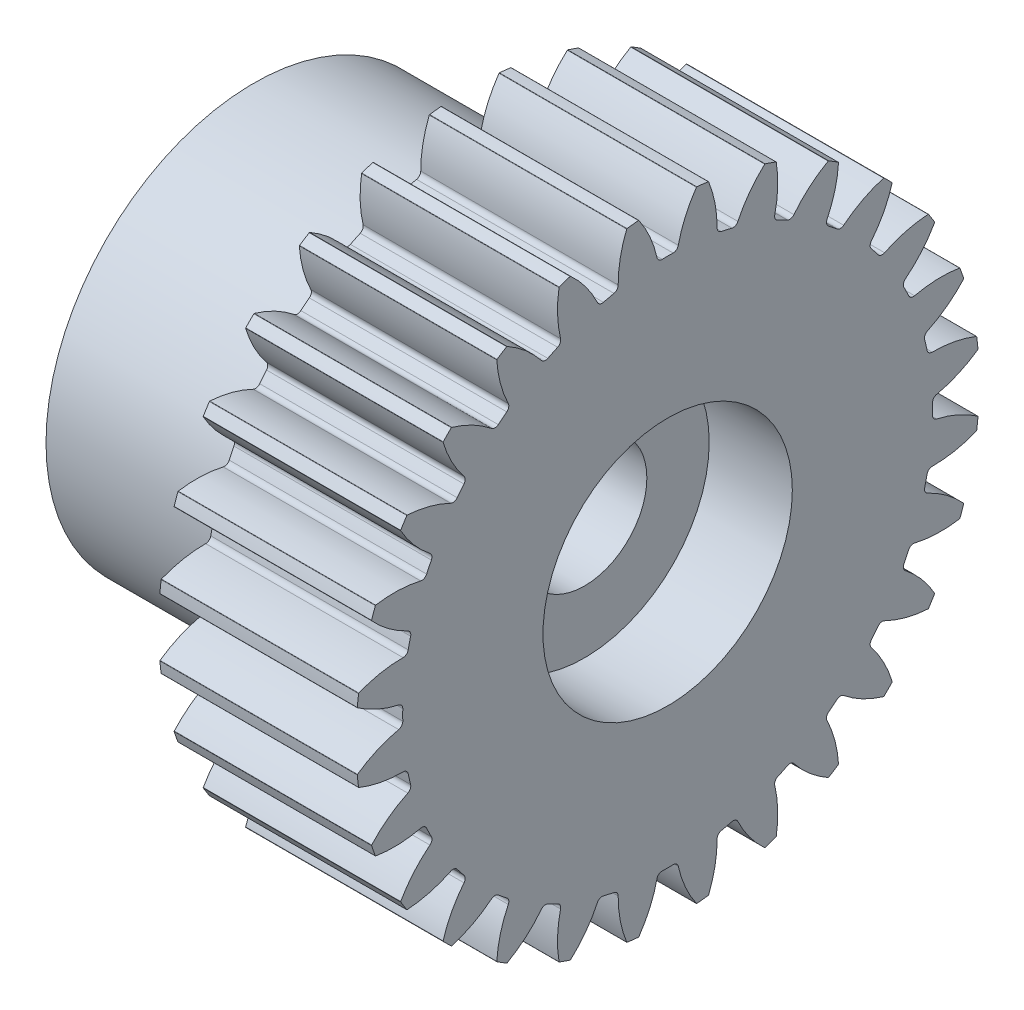
SolidWorks part; units mm, degrees
ref_plane "Plane1" through (0, 0, 0) normal (0, 0, 1) x (1, 0, 0)
ref_plane "Plane2" through (0, 0, 0) normal (0, 1, 0) x (1, 0, 0)
ref_plane "Plane3" through (0, 0, 0) normal (1, 0, 0) x (0, 0, -1)
other "Configuration Table"
sketch "HoldingSke" plane through (0, 0, 0) normal (0, 1, 0) x (1, 0, 0)
  line L0 (0, 0) -> (1.7659, -0.9389)
  line L1 (-15, 0) -> (100, 0) construction
  line L2 (0, 0) -> (-2.1039, 2.3779)
  line L3 (0, 0) -> (-11.863, 4.5341)
  line L4 (0, 0) -> (7.6251, 4.0544)
  line L5 (0, 0) -> (-46.8476, -17.4728)
  line L6 (0, 0) -> (-4.1448, -2.7965)
  line L7 (-2.1039, 2.3779) -> (8.6586, 51.2059)
  line L8 (-76.2, 54.61) -> (-75.9, 54.61)
  line L9 (-71.009, 38.7566) -> (-53.1078, 45.2721)
  line L10 (-76.2, 71.12) -> (104.1128, 71.12)
  line L11 (0, 0) -> (-5, 0)
  line L12 (-76.2, 101.6) -> (-76.181, 101.6)
  line L13 (24.9733, 27.94) -> (52.9518, 28.4284)
  line L14 (24.9733, 27.94) -> (24.9743, 27.94)
  line L15 (24.9733, 27.94) -> (100.4006, 29.5858)
  line L16 (-63.627, -0.5) -> (-12.827, -0.5)
  circle A0 centre (0, 0) radius 1.5
  circle A1 centre (0, 0) radius 6.374
  circle A2 centre (0, 0) radius 37.5
  circle A3 centre (0, 0) radius 1.5
  dimension "Num_teeth" = 28
  dimension "Pitch_radius" = 180.3128
  dimension "Width" = 5
  dimension "Thickness" = 5
sketch "BasProSke" plane through (0, 0, 0) normal (0, 1, 0) x (1, 0, 0)
  line L0 (-10, 0) -> (60, 0) construction
  line L1 (0, 0) -> (0, 7.5)
  line L2 (0, 0) -> (5, 0)
  line L3 (5, 0) -> (5, 7.5)
  line L4 (5, 7.5) -> (0, 7.5)
  dimension "Thickness" = 5
  dimension "Diameter" = 15
revolve "Base-Revolve" add sketch "BasProSke" angle 360 about L0
sketch "TooCutSke" plane through (0, 0, 0) normal (1, 0, 0) x (0, 0, -1)
  line L1 (0, 0) -> (0, 107) construction
  line L2 (0, 0) -> (-0.4257, 6.987) construction
  line L3 (0, 0) -> (-1.5654, 13.8936) construction
  line L4 (-0.4257, 6.987) -> (-0.7827, 6.9468) construction
  arc A0 (0.2356, 6.3696) -> (-0.2356, 6.3696) centre (0, 0) ccw
  arc A1 (0.7134, 7.4915) -> (-0.7134, 7.4915) centre (0, 0) ccw
  circle A2 centre (0, 0) radius 7 construction
  circle A3 centre (0, 0) radius 6.5778 construction
  arc A4 (-0.2356, 6.3696) -> (-0.7134, 7.4915) centre (-2.9887, 5.8597) ccw
  arc A5 (0.7134, 7.4915) -> (0.2356, 6.3696) centre (2.9887, 5.8597) ccw
extrude "ToothCut" cut sketch "TooCutSke" along normal through all
fillet "Breaks" radius 0.01 2 edges at (2.5, 7.4676, -0.6965) (2.5, 7.4676, 0.6965) tangent propagation no
fillet "RootFillets" radius 0.126 2 edges at (2.5, 6.3696, -0.2356) (2.5, 6.3696, 0.2356)
pattern_circular "TeethCuts" count 28 every 12.857 about axis through (-10, 0, 0) along (1, 0, 0) of "ToothCut", "RootFillets", "Breaks"
sketch "HubNeaOneSke" plane through (0, 0, 0) normal (-1, 0, 0) x (0, 0, 1)
  circle A0 centre (0, 0) radius 6.374
  dimension "Diameter" = 12.748
extrude "HubNearOne" add sketch "HubNeaOneSke" along normal blind 5.2067
sketch "HubNeaBotSke" plane through (0, 0, 0) normal (-1, 0, 0) x (0, 0, 1)
  circle A0 centre (0, 0) radius 6.374
  dimension "Diameter" = 12.748
extrude "HubNearBoth" [suppressed] add sketch "HubNeaBotSke" along normal blind 22.5
ref_plane "FarPln" through (5, 0, 0) normal (1, 0, 0) x (0, 0, -1)
sketch "HubFarSke" plane through (5, 0, 0) normal (1, 0, 0) x (0, 0, -1)
  circle A0 centre (0, 0) radius 6.374
  dimension "Diameter" = 12.748
extrude "HubFar" [suppressed] add sketch "HubFarSke" along normal blind 22.5
sketch "BorSke" plane through (0, 0, 0) normal (1, 0, 0) x (0, 0, -1)
  circle A0 centre (0, 0) radius 1.5
  dimension "Diameter" = 3
extrude "Bore" cut sketch "BorSke" along normal mid plane 100.0001
sketch "KeySke" plane through (0, 0, 0) normal (1, 0, 0) x (0, 0, -1)
  line L0 (-0.4, 0) -> (-0.4, 1.8)
  line L1 (-0.4, 1.8) -> (0.4, 1.8)
  line L2 (0.4, 1.8) -> (0.4, 0)
  line L3 (0, 0) -> (0, 34) construction
  line L4 (-0.4, 0) -> (0.4, 0)
  dimension "Width" = 0.8
extrude "Keyway" [suppressed] cut sketch "KeySke" along normal mid plane 100.0001
pattern_circular "Keyway2" [suppressed] count 2 every 90 about axis through (-10, 0, 0) along (1, 0, 0)
sketch "Sketch1" plane through (-5.2067, 0, 0) normal (-1, 0, 0) x (0, 0, 1)
  circle A0 centre (0, 0) radius 6.374
  circle A1 centre (0, 0) radius 5
  dimension "D1" = 10
extrude "Cut-Extrude1" cut sketch "Sketch1" along direction (-1, 0, 0) on the side against the normal up to surface (5.2067 mm away) up to face at (0, 3.6989, -5.8867)
sketch "Sketch2" plane through (5, 0, 0) normal (1, 0, 0) x (0, 0, -1)
  circle A0 centre (0, 0) radius 3
  dimension "D1" = 6
extrude "Cut-Extrude2" cut sketch "Sketch2" against normal blind 2.25
sketch "Sketch5" plane through (-5.2067, 0, 0) normal (-1, 0, 0) x (0, 0, 1)
  line L0 (0, 0) -> (0, 4) construction
  line L1 (0, 0) -> (0.5013, 3.9685) construction
  line L2 (0, 0) -> (0.9812, 3.8778) construction
  line L3 (0, 4.3946) -> (0.4598, 3.6401)
  line L4 (0.4598, 3.6401) -> (1.072, 4.2773)
  line L5 (0, 4.3946) -> (1.072, 4.2773)
  line L6 (1.072, 4.2773) -> (1.3297, 3.4321)
  line L7 (1.3297, 3.4321) -> (2.0811, 3.8971)
  line L8 (2.0811, 3.8971) -> (2.1206, 3.0144)
  line L9 (2.1206, 3.0144) -> (2.964, 3.2779)
  line L10 (2.964, 3.2779) -> (2.7827, 2.4131)
  line L11 (2.7827, 2.4131) -> (3.6651, 2.4585)
  line L12 (3.6651, 2.4585) -> (3.2745, 1.666)
  line L13 (3.2745, 1.666) -> (4.1405, 1.4906)
  line L14 (4.1405, 1.4906) -> (3.565, 0.8201)
  line L15 (3.565, 0.8201) -> (4.3602, 0.4349)
  line L16 (4.3602, 0.4349) -> (3.636, -0.0715)
  line L17 (3.636, -0.0715) -> (4.3104, -0.6424)
  line L18 (4.3104, -0.6424) -> (3.4831, -0.9527)
  line L19 (3.4831, -0.9527) -> (3.9943, -1.6734)
  line L20 (3.9943, -1.6734) -> (3.1158, -1.7682)
  line L21 (3.1158, -1.7682) -> (3.4318, -2.5934)
  line L22 (3.4318, -2.5934) -> (2.5573, -2.4668)
  line L23 (2.5573, -2.4668) -> (2.6581, -3.3446)
  line L24 (2.6581, -3.3446) -> (1.8426, -3.0045)
  line L25 (1.8426, -3.0045) -> (1.7219, -3.8798)
  line L26 (1.7219, -3.8798) -> (1.0166, -3.3475)
  line L27 (1.0166, -3.3475) -> (0.682, -4.1653)
  line L28 (0.682, -4.1653) -> (0.1313, -3.4744)
  line L29 (0.1313, -3.4744) -> (-0.3962, -4.1833)
  line L30 (-0.3962, -4.1833) -> (-0.7578, -3.3771)
  line L31 (-0.7578, -3.3771) -> (-1.445, -3.9326)
  line L32 (-1.445, -3.9326) -> (-1.5948, -3.0618)
  line L33 (-1.5948, -3.0618) -> (-2.3985, -3.4289)
  line L34 (-2.3985, -3.4289) -> (-2.327, -2.5482)
  line L35 (-2.327, -2.5482) -> (-3.1968, -2.7039)
  line L36 (-3.1968, -2.7039) -> (-2.9086, -1.8687)
  line L37 (-2.9086, -1.8687) -> (-3.7897, -1.8032)
  line L38 (-3.7897, -1.8032) -> (-3.3028, -1.0659)
  line L39 (-3.3028, -1.0659) -> (-4.14, -0.7833)
  line L40 (-4.14, -0.7833) -> (-3.485, -0.1903)
  line L41 (-3.485, -0.1903) -> (-4.2257, 0.2916)
  line L42 (-4.2257, 0.2916) -> (-3.4438, 0.7032)
  line L43 (-3.4438, 0.7032) -> (-4.0413, 1.3541)
  line L44 (-4.0413, 1.3541) -> (-3.1816, 1.5583)
  line L45 (-3.1816, 1.5583) -> (-3.5985, 2.3374)
  line L46 (-3.5985, 2.3374) -> (-2.715, 2.3214)
  line L47 (-2.715, 2.3214) -> (-2.9251, 3.1796)
  line L48 (-2.9251, 3.1796) -> (-2.0734, 2.9444)
  line L49 (-2.0734, 2.9444) -> (-2.0633, 3.8279)
  line L50 (-2.0633, 3.8279) -> (-1.2969, 3.3883)
  line L51 (-1.2969, 3.3883) -> (-1.0675, 4.2416)
  line L52 (-1.0675, 4.2416) -> (-0.4344, 3.6251)
  line L53 (-0.4344, 3.6251) -> (0, 4.3946)
  line L54 (0.0718, 0.0932) -> (0.4598, 3.6401) construction
  arc A0 (-2.837, 2.8198) -> (-3.2506, 2.3311) centre (0, 0) ccw
  arc A1 (5.1949, 5.4025) -> (4.2351, 4.8995) centre (5.9901, 2.7178) ccw construction
  arc A2 (5.1949, 5.4025) -> (4.2351, 4.8995) centre (5.9901, 2.7178) ccw
  arc A3 (-3.44, 2.0412) -> (-3.737, 1.4264) centre (0, 0) ccw
  arc A4 (-3.8367, 1.1312) -> (-3.9777, 0.4222) centre (0, 0) ccw
  arc A5 (-3.9974, 0.1431) -> (-3.9526, -0.6137) centre (0, 0) ccw
  arc A6 (-3.9059, -0.8623) -> (-3.6619, -1.6096) centre (0, 0) ccw
  arc A7 (-3.5619, -1.8201) -> (-3.1252, -2.4966) centre (0, 0) ccw
  arc A8 (-2.9824, -2.6656) -> (-2.3811, -3.2141) centre (0, 0) ccw
  arc A9 (-2.2022, -3.3392) -> (-1.4824, -3.7152) centre (0, 0) ccw
  arc A10 (-1.2716, -3.7925) -> (-0.492, -3.9696) centre (0, 0) ccw
  arc A11 (-0.2538, -3.9919) -> (0.5229, -3.9657) centre (0, 0) ccw
  arc A12 (0.7812, -3.923) -> (1.4964, -3.7096) centre (0, 0) ccw
  arc A13 (1.7617, -3.5912) -> (2.3681, -3.2236) centre (0, 0) ccw
  arc A14 (2.621, -3.0216) -> (3.0872, -2.5435) centre (0, 0) ccw
  arc A15 (3.3028, -2.2565) -> (3.614, -1.7144) centre (0, 0) ccw
  arc A16 (3.7652, -1.3503) -> (3.9216, -0.7882) centre (0, 0) ccw
  arc A17 (3.9833, -0.3654) -> (3.9959, 0.1802) centre (0, 0) ccw
  arc A18 (3.9495, 0.6338) -> (3.8355, 1.1353) centre (0, 0) ccw
  arc A19 (3.6724, 1.5854) -> (3.4506, 2.0233) centre (0, 0) ccw
  arc A20 (3.1748, 2.4333) -> (2.8625, 2.7939) centre (0, 0) ccw
  arc A21 (2.4906, 3.13) -> (2.1032, 3.4024) centre (0, 0) ccw
  arc A22 (1.6626, 3.6381) -> (1.2141, 3.8113) centre (0, 0) ccw
  arc A23 (0.7394, 3.9311) -> (0.2451, 3.9925) centre (0, 0) ccw
  arc A24 (-0.2264, 3.9936) -> (-0.7471, 3.9296) centre (0, 0) ccw
  arc A25 (-1.1803, 3.8219) -> (-1.7012, 3.6202) centre (0, 0) ccw
  arc A26 (-2.0679, 3.424) -> (-2.5552, 3.0775) centre (0, 0) ccw
  dimension "D1" = 8
  dimension "D2" = 7.2
  dimension "D3" = 14.2
  dimension "D4" = 0.7
  dimension "D5" = 29.65
  dimension "D6" = 25
  dimension "D7" = 3.5681
extrude "Cut-Extrude5" cut sketch "Sketch5" against normal blind 3.8 contours L53 L52 L51 L50 L49 L48 L47 L46 L45 L44 L43 L42 L41 L40 L39 L38 L37 L36 L35 L34 L33 L32 L31 L30 L29 L28 region at (-5.2067, 0.0932, 0.0718)
sketch "Sketch7" plane through (5, 0, 0) normal (1, 0, 0) x (0, 0, -1)
  circle A0 centre (0, 0) radius 8.7838
extrude "Cut-Extrude6" cut sketch "Sketch7" against normal blind 0.25
equation "' \"Module@HoldingSke\" = 6.35"
equation "' \"Num_teeth@HoldingSke\" = 12"
equation "' \"Ap@HoldingSke\" =  20"
equation "' \"Ap@HoldingSke\" = 20"
equation "' \"Width@HoldingSke\" = 0.5 * 25.4"
equation "' \"Hub_dia@HoldingSke\"= 1 * 25.4"
equation "' \"Hub_dia@HoldingSke\" = 1 * 25.4"
equation "' \"Overall_len@HoldingSke\" = 1.0 * 25.4"
equation "' \"Bore@HoldingSke\" = 0.75 * 25.4"
equation "' \"T_dim@HoldingSke\" = 0.1 * 25.4"
equation "' \"Width@KeySke\" = 0.25 * 25.4"
equation "' \"Show_teeth@HoldingSke\" = 13"
equation "' \"Backlash@HoldingSke\" = 0.009 * 25.4"
equation "' \"Addendum_fac@HoldingSke\" = 1.0"
equation "' \"Dedendum_fac@HoldingSke\" = 1.25"
equation "' \"Dedendum_add@HoldingSke\" = 0.00005 * 25.4"
equation "' \"Clearance_fac@HoldingSke\" = 0.25"
equation "\"Pitch@HoldingSke\" = 1 / \"Module@HoldingSke\""
equation "\"Overcut_dia@TooCutSke\" = (\"Num_teeth@HoldingSke\" + 2 * \"Addendum_fac@HoldingSke\") / \"Pitch@HoldingSke\" + 0.002 * 25.4"
equation "\"Pitch_dia@TooCutSke\" = \"Num_teeth@HoldingSke\" / \"Pitch@HoldingSke\""
equation "\"Base_dia@TooCutSke\" = \"Num_teeth@HoldingSke\" / \"Pitch@HoldingSke\" * cos((\"Ap@HoldingSke\"  * 3.14159265 / 180))"
equation "\"Root_dia@TooCutSke\" = (\"Num_teeth@HoldingSke\" + 2) / \"Pitch@HoldingSke\" - 2 * (\"Addendum_fac@HoldingSke\" + \"Dedendum_fac@HoldingSke\") / \"Pitch@HoldingSke\" - \"Dedendum_add@HoldingSke\" * 2"
equation "\"Half_ang@TooCutSke\" = 180 / \"Num_teeth@HoldingSke\""
equation "\"Half_CT@TooCutSke\" = \"Num_teeth@HoldingSke\" / \"Pitch@HoldingSke\" * sin((3.14159265 / 2 / \"Num_teeth@HoldingSke\")) / 2 - 7 * \"Backlash@HoldingSke\" / 4"
equation "\"Flank_rad@TooCutSke\" = \"Num_teeth@HoldingSke\" / \"Pitch@HoldingSke\" / 5"
equation "\"Radius@RootFillets\" = \"Clearance_fac@HoldingSke\" / \"Pitch@HoldingSke\" + \"Dedendum_add@HoldingSke\""
equation "\"Break_rad@Breaks\" = 0.02 / \"Pitch@HoldingSke\""
equation "\"Thickness@HoldingSke\" = \"Width@HoldingSke\""
equation "\"OAL@HoldingSke\" = \"Thickness@HoldingSke\""
equation "\"MHD@HoldingSke\" = (\"Num_teeth@HoldingSke\" + 2) / \"Pitch@HoldingSke\" - 2 * (\"Addendum_fac@HoldingSke\" + \"Dedendum_fac@HoldingSke\")  / \"Pitch@HoldingSke\" - \"Dedendum_add@HoldingSke\" * 2"
equation "\"MBD@HoldingSke\" = (\"Num_teeth@HoldingSke\" + 2) / \"Pitch@HoldingSke\" - 2 * (\"Addendum_fac@HoldingSke\" + \"Dedendum_fac@HoldingSke\")  / \"Pitch@HoldingSke\" - \"Dedendum_add@HoldingSke\" * 2 - 0.002 * 25.4"
equation "\"MHD@HoldingSke\" = ((sgn( \"MHD@HoldingSke\" - \"Hub_dia@HoldingSke\" )-1)*( \"MHD@HoldingSke\" - \"Hub_dia@HoldingSke\" ))/-2+ \"Hub_dia@HoldingSke\""
equation "\"MBD@HoldingSke\" = ((sgn( \"MBD@HoldingSke\" - \"Bore@HoldingSke\" )-1)*( \"MBD@HoldingSke\" - \"Bore@HoldingSke\" ))/-2+ \"Bore@HoldingSke\""
equation "\"OAL@HoldingSke\" = ((sgn( \"OAL@HoldingSke\" - \"Overall_len@HoldingSke\" )+1)*( \"OAL@HoldingSke\" - \"Overall_len@HoldingSke\" ))/2 + \"Overall_len@HoldingSke\" + 0.000002 * 25.4"
equation "\"Num_teeth@TeethCuts\" = int( \"Show_teeth@HoldingSke\" ) + 1"
equation "\"Num_teeth@TeethCuts\" = ((sgn( \"Num_teeth@TeethCuts\" - \"Num_teeth@HoldingSke\" )-1)*( \"Num_teeth@TeethCuts\" - \"Num_teeth@HoldingSke\" ))/-2+ \"Num_teeth@HoldingSke\""
equation "\"Num_teeth@TeethCuts\" = ((sgn( \"Num_teeth@TeethCuts\" - 2.0)+1)*( \"Num_teeth@TeethCuts\" - 2.0))/2 +2.0"
equation "\"Angle@TeethCuts\" = 360.0 / \"Num_teeth@HoldingSke\""
equation "\"Diameter@BasProSke\" = (\"Num_teeth@HoldingSke\" + 2 * \"Addendum_fac@HoldingSke\") / \"Pitch@HoldingSke\""
equation "\"Thickness@BasProSke\"  = \"Thickness@HoldingSke\""
equation "' \"Fillet_rad@BasProSke\" =  \"Thickness@HoldingSke\" * 0.05"
equation "' \"Fillet_rad@BasProSke\" = \"Thickness@HoldingSke\" * 0.05"
equation "\"MHD@HoldingSke\" = ((sgn( \"MHD@HoldingSke\" - \"Root_dia@TooCutSke\" )-1)*( \"MHD@HoldingSke\" - \"Root_dia@TooCutSke\" ))/-2+ \"Root_dia@TooCutSke\""
equation "\"Diameter@HubNeaOneSke\" = \"MHD@HoldingSke\""
equation "\"Diameter@HubNeaBotSke\" = \"MHD@HoldingSke\""
equation "\"Length@HubNearBoth\" = ( \"OAL@HoldingSke\" - \"Thickness@BasProSke\" ) / 2.0"
equation "\"Thickness@FarPln\" = \"Thickness@BasProSke\""
equation "\"Diameter@HubFarSke\" = \"MHD@HoldingSke\""
equation "\"Length@HubFar\" = ( \"OAL@HoldingSke\" - \"Thickness@BasProSke\" ) / 2.0"
equation "\"Diameter@BorSke\" = \"MBD@HoldingSke\""
equation "\"D1@Bore\" = \"OAL@HoldingSke\" * 2.0"
equation "\"D1@Keyway\" = \"OAL@HoldingSke\" * 2.0"
equation "\"Offset@KeySke\" = \"T_dim@HoldingSke\" + \"MBD@HoldingSke\" / 2.0"
